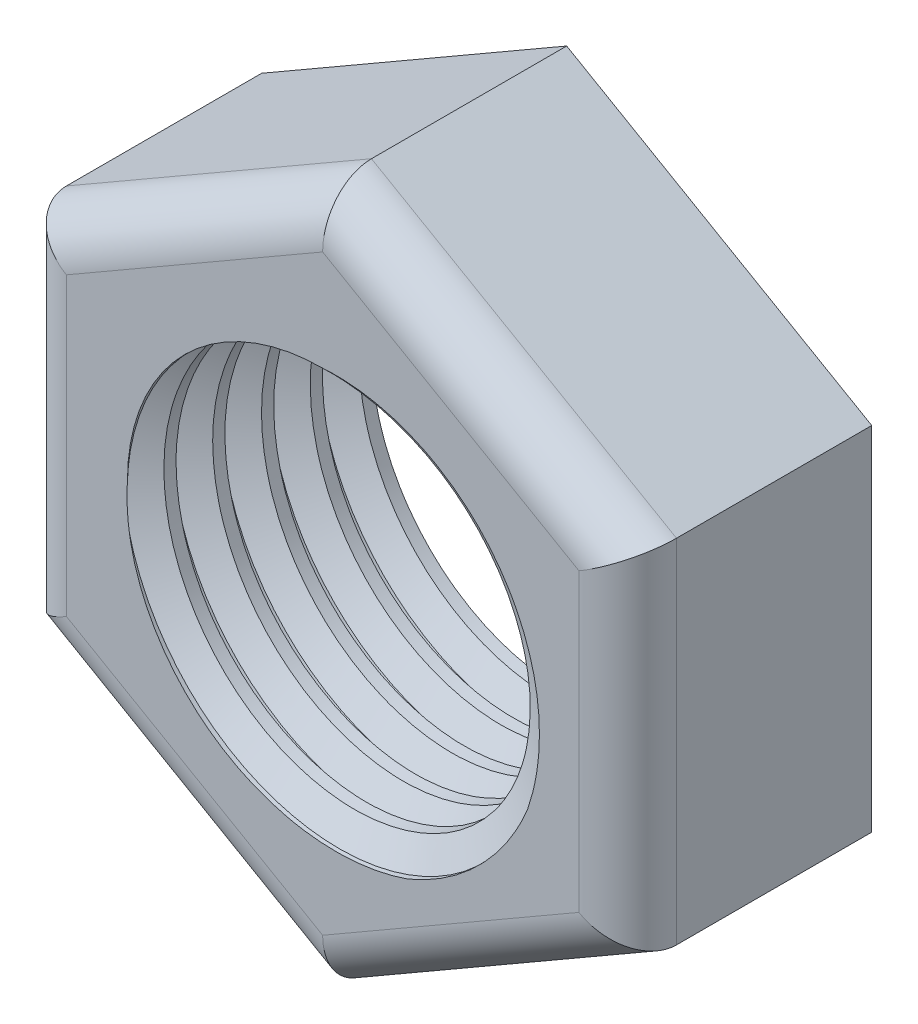
SolidWorks part; units mm, degrees
ref_plane "Front Plane" through (0, 0, 0) normal (0, 0, 1) x (1, 0, 0)
ref_plane "Top Plane" through (0, 0, 0) normal (0, 1, 0) x (1, 0, 0)
ref_plane "Right Plane" through (0, 0, 0) normal (1, 0, 0) x (0, 0, -1)
sketch "Sketch1" plane through (0, 0, 0) normal (0, 0, 1) x (1, 0, 0)
  line L1 (0, -14.4338) -> (12.5, -7.2169)
  line L2 (12.5, -7.2169) -> (12.5, 7.2169)
  line L3 (12.5, 7.2169) -> (0, 14.4338)
  line L4 (0, 14.4338) -> (-12.5, 7.2169)
  line L5 (-12.5, 7.2169) -> (-12.5, -7.2169)
  line L6 (-12.5, -7.2169) -> (0, -14.4338)
  circle A0 centre (0, 0) radius 12.5 construction
  circle A1 centre (0, 0) radius 8
  dimension "D2" = 16
  dimension "D1" = 25
extrude "Boss-Extrude2" add sketch "Sketch1" along normal blind 10
thread "Thread1" pitch 2 start angle 0, offset 10, length 12, pitch 2, diameter 16
ref_plane "Plane2" through (-8, 0, 0) normal (0, -1, 0) x (-1, 0, 0)
sketch "Thread Profile2" plane through (-8, 0, 0) normal (0, -1, 0) x (-1, 0, 0)
  line L0 (0, 0) -> (0, 2) construction
  line L1 (0, 0) -> (1.0825, 0.625)
  line L2 (1.0825, 0.625) -> (1.0825, 0.875)
  line L3 (1.0825, 0.875) -> (0, 1.5)
  line L4 (1.0825, 0.75) -> (0, 0.75) construction
  line L11 (0, 0) -> (0, 1.5)
  point P2 (0, 0)
  dimension "Pitch" = 2
  dimension "Profile_Angle" = 60
  dimension "Profile_Land" = 0.25
  dimension "Profile_Height" = 1.0825
fillet "Fillet3" radius 2 6 edges at (6.25, 10.8253, 10) (-6.25, 10.8253, 10) (-12.5, 0, 10) (-6.25, -10.8253, 10) (6.25, -10.8253, 10) (12.5, 0, 10)
